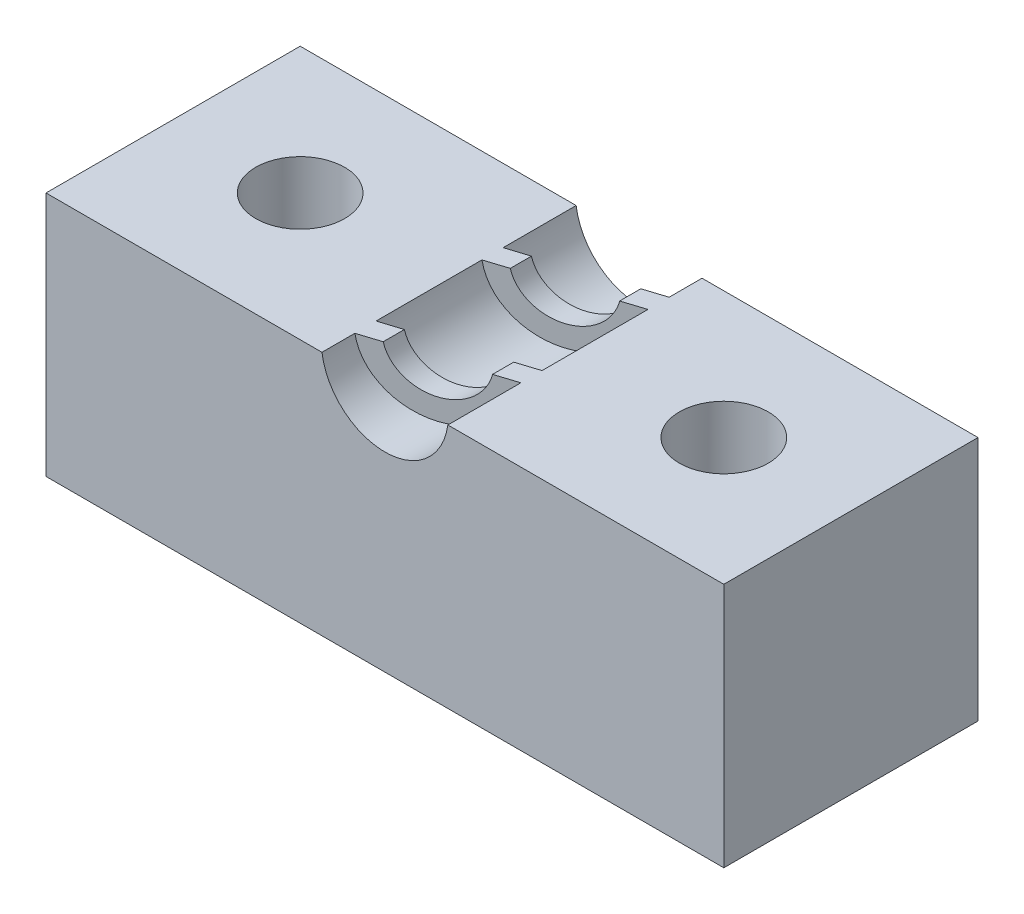
SolidWorks part; units mm, degrees
ref_plane "前视基准面" through (0, 0, 0) normal (0, 0, 1) x (1, 0, 0)
ref_plane "上视基准面" through (0, 0, 0) normal (0, 1, 0) x (1, 0, 0)
ref_plane "右视基准面" through (0, 0, 0) normal (1, 0, 0) x (0, 0, -1)
other "Configuration Table"
sketch "草图1" plane through (0, 0, 0) normal (0, 0, 1) x (1, 0, 0)
  line L1 (-8, -6) -> (8, -6)
  line L2 (-8, -6) -> (-8, 6)
  line L3 (-8, 6) -> (8, 6)
  line L4 (8, -6) -> (8, 6)
  line L5 (-8, -6) -> (8, 6) construction
  line L6 (-8, 6) -> (8, -6) construction
  circle A0 centre (0, 0) radius 1.5
  point P0 (0, 0)
  dimension "D3" = 3
  dimension "D1" = 16
  dimension "D2" = 12
extrude "凸台-拉伸1" add sketch "草图1" along normal mid plane 6
sketch "草图2" plane through (0, 0, 3) normal (0, 0, 1) x (1, 0, 0)
  circle A0 centre (0, 0) radius 1.5 construction
  circle A1 centre (0, 0) radius 1.5
curve "螺旋线/涡状线1" [suppressed] pitch 3 height 6 turns 2
sketch "草图4" [suppressed] plane through (0, 0, 0) normal (0, 1, 0) x (1, 0, 0)
  line L0 (0, 4.8801) -> (0, -4.2719) construction
sketch3d "3D草图1" [suppressed]
  spline S0 degree 3 poles (-942.1956, -331.2134, -36.5595) (37.1464, -47.6823, 7.9547) (5.73, 5.65, 5.1859) (-1.0881, 1.0883, 2.625) (-1.4219, 0.589, 2.4375) (-1.539, 0, 2.25) (-1.4219, -0.589, 2.0625) (-1.0883, -1.0883, 1.875) (-0.589, -1.4219, 1.6875) (0, -1.5391, 1.5) (0.589, -1.4219, 1.3125) (1.0883, -1.0883, 1.125) (1.4219, -0.589, 0.9375) (1.5391, 0, 0.75) (1.4219, 0.589, 0.5625) (1.0883, 1.0883, 0.375) (0.589, 1.4219, 0.1875) (0, 1.5391, 0) (-0.589, 1.4219, -0.1875) (-1.0883, 1.0883, -0.375) (-1.4219, 0.589, -0.5625) (-1.5391, 0, -0.75) (-1.4219, -0.589, -0.9375) (-1.0883, -1.0883, -1.125) (-0.589, -1.4219, -1.3125) (0, -1.5391, -1.5) (0.589, -1.4219, -1.6875) (1.0883, -1.0883, -1.875) (1.4219, -0.589, -2.0625) (1.539, 0, -2.25) (1.4219, 0.589, -2.4375) (1.0881, 1.0883, -2.625) (-5.73, 5.65, -5.1859) (-37.1462, -47.6821, -7.9547) (942.1897, -331.2117, 36.5592) knots -1.18812 -1.18812 -1.18812 -1.18812 0.03125 0.0625 0.09375 0.125 0.15625 0.1875 0.21875 0.25 0.28125 0.3125 0.34375 0.375 0.40625 0.4375 0.46875 0.5 0.53125 0.5625 0.59375 0.625 0.65625 0.6875 0.71875 0.75 0.78125 0.8125 0.84375 0.875 0.90625 0.9375 0.96875 2.188117 2.188117 2.188117 2.188117 only from (0, 1.5, 3) to (0, 1.5, -3) construction
  spline S1 degree 3 poles (0, 1.5, 3) (-0.1952, 1.5, 2.9379) (-0.5895, 1.4219, 2.8123) (-1.0881, 1.0883, 2.625) (-1.4219, 0.589, 2.4375) (-1.539, 0, 2.25) (-1.4219, -0.589, 2.0625) (-1.0883, -1.0883, 1.875) (-0.589, -1.4219, 1.6875) (0, -1.5391, 1.5) (0.589, -1.4219, 1.3125) (1.0883, -1.0883, 1.125) (1.4219, -0.589, 0.9375) (1.5391, 0, 0.75) (1.4219, 0.589, 0.5625) (1.0883, 1.0883, 0.375) (0.589, 1.4219, 0.1875) (0, 1.5391, 0) (-0.589, 1.4219, -0.1875) (-1.0883, 1.0883, -0.375) (-1.4219, 0.589, -0.5625) (-1.5391, 0, -0.75) (-1.4219, -0.589, -0.9375) (-1.0883, -1.0883, -1.125) (-0.589, -1.4219, -1.3125) (0, -1.5391, -1.5) (0.589, -1.4219, -1.6875) (1.0883, -1.0883, -1.875) (1.4219, -0.589, -2.0625) (1.539, 0, -2.25) (1.4219, 0.589, -2.4375) (1.0881, 1.0883, -2.625) (0.5895, 1.4219, -2.8123) (0.1952, 1.5, -2.9379) (0, 1.5, -3) knots 0 0 0 0 0.03125 0.0625 0.09375 0.125 0.15625 0.1875 0.21875 0.25 0.28125 0.3125 0.34375 0.375 0.40625 0.4375 0.46875 0.5 0.53125 0.5625 0.59375 0.625 0.65625 0.6875 0.71875 0.75 0.78125 0.8125 0.84375 0.875 0.90625 0.9375 0.96875 1 1 1 1
sketch3d "3D草图2" [suppressed]
  line L0 (0, 1.5, 3) -> (0, 0, 3) construction
  line L1 (0, 0, -4.8801) -> (0, 0, 4.2719) construction
  line L2 (0, 1.5, 3) -> (0, 0.3536, 3)
surface "曲面-扫描1" [suppressed]
thicken "加厚3" [suppressed] surfaces to thicken 107 thickness 0.225 parameters "D1"=0.225
sketch "草图6" plane through (0, 0, 0) normal (0, 1, 0) x (1, 0, 0)
  line L0 (-1.5, -3) -> (1.5, -3) construction
  line L1 (1.5, 3) -> (-1.5, 3) construction
  line L2 (-1.5, -3) -> (1.5, -3)
  line L3 (1.5, 3) -> (-1.5, 3)
  line L4 (-1.5, 3) -> (-1.5, -3)
  line L5 (1.5, -3) -> (1.5, 3)
  line L6 (-1.5, 0.7724) -> (1.5, 1.7276)
  line L7 (1.5, 1.7276) -> (1.5, 2.2276)
  line L8 (1.5, 2.2276) -> (-1.5, 1.2724)
  line L9 (-1.5, -1.7276) -> (1.5, -0.7724)
  line L10 (-1.5, -2.2276) -> (1.5, -1.2724)
  line L11 (-2.0945, -0.6668) -> (3.135, 0.9981) construction
  line L12 (-3.1004, 0) -> (4.2723, 0) construction
  point P15 (-1.5, -1.4303)
  point P19 (-1.5, -1.3448)
  point P20 (-1.5, -2.1906)
  dimension "D1" = 2.5
  dimension "D2" = 0.5
  dimension "D3" = 0.5
  dimension "D4" = 17.66
extrude "凸台-拉伸2" add sketch "草图6" against normal up to surface (6 mm away) contours L4 L10 L5 L9 | L5 L8 L4 L6 region at (0, 0, 1.5) region at (0, 0, -1.5) up to face at (0, -6, 0)
sketch "草图7" plane through (0, 0, 0) normal (0, 0, 1) x (1, 0, 0)
  line L0 (0, 0) -> (-0.979, -0.2039)
  line L1 (0, 0) -> (0.979, -0.2039)
  line L2 (-0.979, -0.2039) -> (-8, -0.2039)
  line L3 (0.979, -0.2039) -> (8, -0.2039)
  line L6 (8, -6) -> (8, 6)
  line L7 (-8, -6) -> (8, -6)
  line L8 (-8, 6) -> (-8, -6)
  line L9 (8, 6) -> (-8, 6)
  line L10 (8, -6) -> (8, 6)
  line L11 (-8, -6) -> (8, -6)
  line L12 (-8, 6) -> (-8, -6)
  line L13 (8, 6) -> (-8, 6)
  circle A0 centre (0, 0) radius 1
  dimension "D1" = 2
  dimension "D2" = 0
  dimension "D3" = 156.47
extrude "切除-拉伸2" cut sketch "草图7" against normal through all both and the other way through all contours A0 L3 L10 L13 L12 L2 | L1 A0 L0 | L0 A0 L1 region at (0, -0.478, 0) region at (0, 0.3675, 0) region at (0, 2.9505, 0)
sketch "草图8" plane through (0, 0, 0) normal (0, 1, 0) x (1, 0, 0)
  line L0 (0, 5.5834) -> (0, -5.0797) construction
  circle A0 centre (-5, 0) radius 1.05
  circle A1 centre (5, 0) radius 1.05
  point P4 (0, 0)
  point P8 (5, 0.8221)
  point P9 (0, 0)
  dimension "D1" = 2.1
  dimension "D2" = 2.1
  dimension "D3" = 10
extrude "切除-拉伸3" cut sketch "草图8" against normal through all
equation "\"x\"=0.8094"
